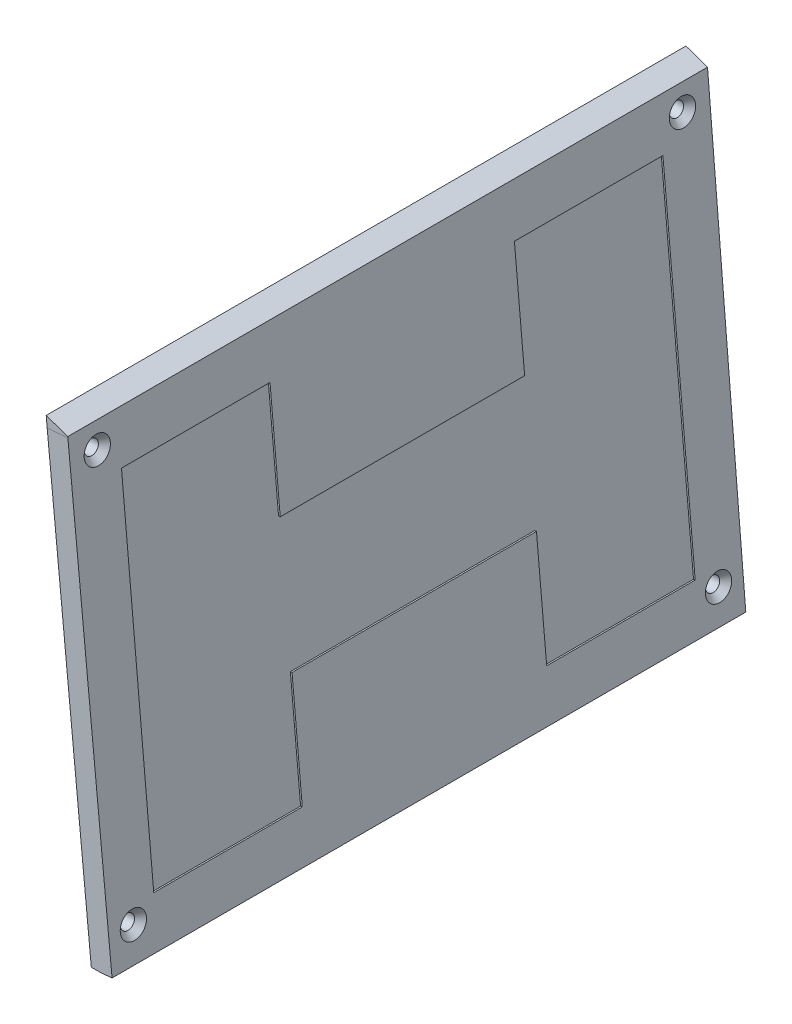
SolidWorks part; units mm, degrees
ref_plane "Front Plane" through (0, 0, 0) normal (0, 0, 1) x (1, 0, 0)
ref_plane "Top Plane" through (0, 0, 0) normal (0, 1, 0) x (1, 0, 0)
ref_plane "Right Plane" through (0, 0, 0) normal (1, 0, 0) x (0, 0, -1)
sketch "Sketch3" plane through (0, 0, 0) normal (0, 1, 0) x (1, 0, 0)
  line L1 (-180, 95) -> (180, 95)
  line L2 (-180, 95) -> (-180, -95)
  line L3 (-180, -95) -> (180, -95)
  line L4 (180, 95) -> (180, -95)
  line L5 (-180, 95) -> (180, -95) construction
  line L6 (-180, -95) -> (180, 95) construction
  point P0 (0, 0)
  dimension "D1" = 190
  dimension "D2" = 360
extrude "Boss-Extrude2" add sketch "Sketch3" along normal blind 158
sketch "Sketch4" plane through (180, 0, 0) normal (1, 0, 0) x (0, 0, -1)
  line L0 (-95, 0) -> (-95, 158)
  line L1 (-95, 158) -> (-85, 158)
  line L2 (-95, 158) -> (95, 158) construction
  line L3 (-85, 158) -> (-95, 0)
  line L4 (0, 0) -> (0, 123.75) construction
  line L5 (85, 158) -> (95, 0)
  line L6 (95, 158) -> (85, 158)
  line L7 (95, 0) -> (95, 158)
  dimension "D1" = 170
extrude "Cut-Extrude1" cut sketch "Sketch4" against normal through all
sketch "Sketch5" plane through (0, 0, 0) normal (0, 0, 1) x (1, 0, 0)
  line L0 (-180, 0) -> (-165.5, 158)
  line L1 (-180, 158) -> (180, 158) construction
  line L2 (-165.5, 158) -> (-180, 158)
  line L3 (-180, 158) -> (-180, 0)
  line L4 (0, 0) -> (0, 158) construction
  line L5 (180, 158) -> (180, 0)
  line L6 (165.5, 158) -> (180, 158)
  line L7 (180, 0) -> (165.5, 158)
  dimension "D1" = 331
extrude "Cut-Extrude2" cut sketch "Sketch5" against normal through all both and the other way through all
sketch "Sketch6" plane through (0, 0, 0) normal (0, 0, 1) x (1, 0, 0)
  line L0 (180, 0) -> (180, 105) construction
  line L2 (-165.5, 158) -> (165.5, 158) construction
  line L3 (64, 145.6686) -> (180, 105)
  line L4 (180, 105) -> (180, 158)
  line L5 (-180, 110) -> (-180, 158)
  line L6 (-180, 158) -> (-97, 158)
  line L8 (-180, 0) -> (-180, 110) construction
  line L9 (64, 145.6686) -> (64, 158)
  line L10 (64, 158) -> (180, 158)
  line L11 (-180, 110) -> (-97, 145.6686)
  line L12 (-97, 145.6686) -> (-97, 158)
  dimension "D1" = 105
  dimension "D2" = 110
  dimension "D3" = 83
  dimension "D4" = 116
extrude "Cut-Extrude3" cut sketch "Sketch6" along normal through all both and the other way through all
sketch "Sketch8" plane through (0, 0, 0) normal (0, 1, 0) x (1, 0, 0)
  line L0 (-180, 76.5) -> (-97, 85)
  line L3 (-180, 95) -> (-180, -95) construction
  line L4 (-180, 111.8161) -> (-180, 76.5)
  line L5 (0, 0) -> (-198.7212, 0) construction
  line L11 (-180, 111.8161) -> (-97, 111.8161)
  line L12 (-97, 111.8161) -> (-97, 85)
  line L13 (-97, -111.8161) -> (-97, -85)
  line L14 (-180, -111.8161) -> (-97, -111.8161)
  line L15 (-180, -111.8161) -> (-180, -76.5)
  line L16 (-180, -76.5) -> (-97, -85)
  line L17 (64, 85) -> (64, 140.1812)
  line L18 (64, 85) -> (180, 76.5)
  line L19 (180, 76.5) -> (197.104, 166.0233)
  line L20 (197.104, 166.0233) -> (64, 140.1812)
  line L21 (197.104, -166.0233) -> (64, -140.1812)
  line L22 (180, -76.5) -> (197.104, -166.0233)
  line L23 (64, -85) -> (180, -76.5)
  line L24 (64, -85) -> (64, -140.1812)
  line L29 (180, -95) -> (180, 95) construction
  dimension "D1" = 153
extrude "Cut-Extrude4" cut sketch "Sketch8" against normal through all and the other way through all
sketch "Sketch10" plane through (0, 0, 0) normal (0, -1, 0) x (1, 0, 0)
  line L1 (-156.5, -79) -> (156.5, -79) construction
  line L2 (-156.5, -79) -> (-156.5, 79) construction
  line L3 (-156.5, 79) -> (156.5, 79) construction
  line L4 (156.5, -79) -> (156.5, 79) construction
  line L5 (-156.5, -79) -> (156.5, 79) construction
  line L6 (-156.5, 79) -> (156.5, -79) construction
  point P0 (0, 0)
  dimension "D1" = 313
  dimension "D2" = 158
shell "Shell6" thickness 5 removed face at (-11, 0, 0)
sketch "Sketch11" plane through (0, 0, 0) normal (0, -1, 0) x (1, 0, 0)
  line L0 (-97, 95) -> (64, 95) construction
  line L1 (-97, 95) -> (64, 95)
  line L14 (-97, 95) -> (-97, 85)
  line L15 (-97, 85) -> (-180, 76.5)
  line L16 (-180, 76.5) -> (-180, -76.5)
  line L17 (-180, -76.5) -> (-97, -85)
  line L18 (-97, -85) -> (-97, -95)
  line L19 (-97, -95) -> (64, -95)
  line L20 (64, -95) -> (64, -85)
  line L21 (64, -85) -> (180, -76.5)
  line L22 (180, -76.5) -> (180, 76.5)
  line L23 (180, 76.5) -> (64, 85)
  line L24 (64, 85) -> (64, 95)
  line L25 (64, 95) -> (-97, 95)
  line L26 (-97, 95) -> (-97, 85)
  line L27 (-97, 85) -> (-180, 76.5)
  line L28 (-180, 76.5) -> (-180, -76.5)
  line L29 (-180, -76.5) -> (-97, -85)
  line L30 (-97, -85) -> (-97, -95)
  line L31 (-97, -95) -> (64, -95)
  line L32 (64, -95) -> (64, -85)
  line L33 (64, -85) -> (180, -76.5)
  line L34 (180, -76.5) -> (180, 76.5)
  line L35 (180, 76.5) -> (64, 85)
  line L36 (64, 85) -> (64, 95)
  line L37 (64, 95) -> (-97, 95)
  line M25 (-92, 80.4859) -> (-92, 89.99)
  line M26 (-92, 89.99) -> (59, 89.99)
  line M27 (59, 89.99) -> (59, 80.353)
  line M28 (59, 80.353) -> (174.979, 71.8545)
  line M29 (174.979, 71.8545) -> (174.979, -71.8545)
  line M30 (174.979, -71.8545) -> (59, -80.353)
  line M31 (59, -80.353) -> (59, -89.99)
  line M32 (59, -89.99) -> (-92, -89.99)
  line M33 (-92, -89.99) -> (-92, -80.4859)
  line M34 (-92, -80.4859) -> (-174.979, -71.988)
  line M35 (-174.979, -71.988) -> (-174.979, 71.988)
  line M36 (-174.979, 71.988) -> (-92, 80.4859)
  dimension "D1" = 0
extrude "Boss-Extrude3" add sketch "Sketch11" against normal blind 5 contours M25 M36 M35 M34 M33 M32 M31 M30 M29 M28 M27 M26 region at (-1.4169, 0, 0)
chamfer "Chamfer1" distance 19.9 angle 25 2 edges at (-97, 72.8343, -85) (64, 72.8343, 85) first distance on face at (-97, 75.9172, 0) first distance on face at (64, 75.9172, 0)
chamfer "Chamfer2" distance 19.9 angle 25 2 edges at (-97, 72.8343, 85) (64, 72.8343, -85) first distance on face at (-97, 101.2229, 29.8699) first distance on face at (64, 101.2229, -29.8699)
chamfer "Chamfer3" distance 10 angle 45 2 edges at (73.6078, 71.1501, -84.296) (-106.7449, 70.7404, 84.002) first distance on face at (124.3148, 62.6977, -80.5804) first distance on face at (-140.7451, 63.9993, 80.5201)
chamfer "Chamfer4" distance 5 angle 50 1 edges at (-97, 145.6686, 0) first distance on face at (-122.0326, 134.911, -0.0994)
chamfer "Chamfer5" distance 6 angle 50 1 edges at (64, 145.6686, 0) first distance on face at (97.4296, 133.9485, 0.0677)
sketch "Sketch18" plane through (-9.6212, 0, 93.9484) normal (-0.1019, 0, 0.9948) x (0.9948, 0, 0.1019)
  line L0 (-160.4966, 116.7807) -> (-170.6066, 7.1902)
  line L1 (-171.2699, 0) -> (-160.7055, 114.5163) construction
  line L2 (-170.6066, 7.1902) -> (-129.9277, 7.1902)
  line L3 (-129.9277, 7.1902) -> (-126.2803, 17.3621)
  line L4 (-126.2803, 17.3621) -> (-115.3442, 17.3621)
  line L5 (-115.3442, 17.3621) -> (-115.3442, 136.0837)
  line L7 (-115.3442, 136.0837) -> (-160.4966, 116.7807)
  line L11 (-107.6316, 0) -> (-171.2699, 0) construction
  line L12 (-107.6316, 0) -> (-107.6316, 137.2058) construction
  line L14 (-107.6316, 137.2058) -> (-160.7055, 114.5163) construction
  dimension "D1" = 2
extrude "Boss-Extrude5" add sketch "Sketch18" along normal blind 2
sketch "Sketch19" plane through (-9.825, 0, 95.938) normal (-0.1019, 0, 0.9948) x (0.9948, 0, 0.1019)
  line L0 (-144.8175, 92.3146) -> (-144.8175, 71.3428)
  line L1 (-143.3175, 94.3146) -> (-122.3457, 94.3146)
  line L2 (-145.3175, 92.3146) -> (-145.3175, 71.3428)
  line L3 (-143.3175, 69.3428) -> (-122.3457, 69.3428)
  line L4 (-120.3457, 92.3146) -> (-120.3457, 71.3428)
  line L5 (-145.3175, 94.3146) -> (-122.3457, 69.3428) construction
  line L6 (-145.3175, 69.3428) -> (-120.3457, 94.3146) construction
  line L7 (-143.3175, 69.8428) -> (-122.3457, 69.8428)
  line L8 (-120.8457, 92.3146) -> (-120.8457, 71.3428)
  line L9 (-143.3175, 93.8146) -> (-122.3457, 93.8146)
  arc A0 (-122.3457, 94.3146) -> (-120.3457, 92.3146) centre (-122.3457, 92.3146) cw
  arc A1 (-122.3457, 69.3428) -> (-120.3457, 71.3428) centre (-122.3457, 71.3428) ccw
  arc A2 (-145.3175, 71.3428) -> (-143.3175, 69.3428) centre (-143.3175, 71.3428) ccw
  arc A3 (-143.3175, 94.3146) -> (-145.3175, 92.3146) centre (-143.3175, 92.3146) ccw
  arc A4 (-144.8175, 71.3428) -> (-143.3175, 69.8428) centre (-143.3175, 71.3428) ccw
  arc A5 (-122.3457, 69.8428) -> (-120.8457, 71.3428) centre (-122.3457, 71.3428) ccw
  arc A6 (-122.3457, 93.8146) -> (-120.8457, 92.3146) centre (-122.3457, 92.3146) cw
  arc A7 (-143.3175, 93.8146) -> (-144.8175, 92.3146) centre (-143.3175, 92.3146) ccw
  point P0 (-133.3524, 81.3079)
  dimension "D1" = 2
  dimension "D2" = 0.5
extrude "Cut-Extrude5" cut sketch "Sketch19" against normal blind 0.5
sketch "Sketch20" plane through (0, 5.9887, 94.621) normal (0, 0.0632, 0.998) x (1, 0, 0)
  line L0 (-89.2026, 82.2629) -> (-89.2026, 21.0896)
  line L1 (-86.7026, 83.7629) -> (58.7101, 83.7629)
  line L2 (-88.7026, 81.7629) -> (-88.7026, 21.5896)
  line L3 (-86.7026, 19.5896) -> (58.7101, 19.5896)
  line L4 (60.7101, 81.7629) -> (60.7101, 21.5896)
  line L5 (-88.7026, 83.7629) -> (60.7101, 19.5896) construction
  line L6 (-88.7026, 19.5896) -> (60.7101, 83.7629) construction
  line L7 (-87.2026, 19.0896) -> (59.2101, 19.0896)
  line L8 (61.2101, 82.2629) -> (61.2101, 21.0896)
  line L9 (-87.2026, 84.2629) -> (59.2101, 84.2629)
  line L10 (61.2101, 84.2629) -> (61.2101, 19.0896) construction
  line L11 (-89.2026, 84.2629) -> (61.2101, 84.2629) construction
  line L12 (-88.7026, 83.7629) -> (60.7101, 83.7629) construction
  line L13 (60.7101, 83.7629) -> (60.7101, 19.5896) construction
  line L14 (-88.7026, 19.5896) -> (60.7101, 19.5896) construction
  line L15 (-89.2026, 19.0896) -> (61.2101, 19.0896) construction
  line L16 (-89.2026, 84.2629) -> (-89.2026, 19.0896) construction
  line L17 (-88.7026, 83.7629) -> (-88.7026, 19.5896) construction
  arc A0 (61.2101, 82.2629) -> (59.2101, 84.2629) centre (59.2101, 82.2629) ccw
  arc A1 (58.7101, 83.7629) -> (60.7101, 81.7629) centre (58.7101, 81.7629) cw
  arc A2 (58.7101, 19.5896) -> (60.7101, 21.5896) centre (58.7101, 21.5896) ccw
  arc A3 (59.2101, 19.0896) -> (61.2101, 21.0896) centre (59.2101, 21.0896) ccw
  arc A4 (-89.2026, 21.0896) -> (-87.2026, 19.0896) centre (-87.2026, 21.0896) ccw
  arc A5 (-88.7026, 21.5896) -> (-86.7026, 19.5896) centre (-86.7026, 21.5896) ccw
  arc A6 (-89.2026, 82.2629) -> (-87.2026, 84.2629) centre (-87.2026, 82.2629) cw
  arc A7 (-86.7026, 83.7629) -> (-88.7026, 81.7629) centre (-86.7026, 81.7629) ccw
  point P0 (-13.9963, 51.6763)
  dimension "D2" = 2
  dimension "D1" = 0.5
extrude "Cut-Extrude6" cut sketch "Sketch20" against normal blind 0.5
sketch "Sketch21" plane through (6.537, 0, 89.2107) normal (0.0731, 0, 0.9973) x (0.9973, 0, -0.0731)
  line L0 (78.6105, 140.2638) -> (78.6105, 9.5077)
  line L2 (163.945, 108.4906) -> (173.9281, 0) construction
  line L3 (171.9049, 21.987) -> (163.7609, 110.4906)
  line L4 (163.7609, 110.4906) -> (78.6105, 140.2638)
  line L6 (67.2506, 142.3002) -> (67.2506, 0) construction
  line L8 (78.6105, 9.5077) -> (125.3303, 9.5077)
  line L9 (125.3303, 9.5077) -> (138.5436, 21.987)
  line L10 (138.5436, 21.987) -> (171.9049, 21.987)
  line L11 (163.945, 108.4906) -> (67.2506, 142.3002) construction
  line L12 (163.945, 108.4906) -> (175.2328, 108.4906) construction
  dimension "D1" = 2
extrude "Boss-Extrude6" add sketch "Sketch21" along normal blind 2
sketch "Sketch22" plane through (6.6831, 0, 91.2053) normal (0.0731, 0, 0.9973) x (0.9973, 0, -0.0731)
  line L0 (99.9186, 58.3939) -> (99.9186, 31.5005)
  line L1 (90.1817, 112.8938) -> (113.9275, 112.8938)
  line L2 (88.1817, 110.8938) -> (88.1817, 86.2383)
  line L3 (90.1817, 84.2383) -> (113.9275, 84.2383)
  line L4 (115.9275, 110.8938) -> (115.9275, 86.2383)
  line L5 (88.1817, 112.8938) -> (115.9275, 84.2383) construction
  line L6 (88.1817, 84.2383) -> (115.9275, 112.8938) construction
  line L7 (102.4186, 60.3939) -> (157.9396, 60.3939)
  line L8 (100.4186, 58.3939) -> (100.4186, 31.5005)
  line L9 (102.4186, 29.5005) -> (157.9396, 29.5005)
  line L10 (159.9396, 58.3939) -> (159.9396, 31.5005)
  line L11 (100.4186, 60.3939) -> (159.9396, 29.5005) construction
  line L12 (100.4186, 29.5005) -> (159.9396, 60.3939) construction
  line L13 (144.9909, 57.8533) -> (153.382, 57.8533)
  line L14 (143.9909, 56.8533) -> (143.9909, 52.772)
  line L15 (144.9909, 51.772) -> (153.382, 51.772)
  line L16 (154.382, 56.8533) -> (154.382, 52.772)
  line L17 (143.9909, 57.8533) -> (154.382, 51.772) construction
  line L18 (143.9909, 51.772) -> (154.382, 57.8533) construction
  line L19 (144.9909, 38.1224) -> (153.382, 38.1224)
  line L20 (143.9909, 37.1224) -> (143.9909, 33.0411)
  line L21 (144.9909, 32.0411) -> (153.382, 32.0411)
  line L22 (154.382, 37.1224) -> (154.382, 33.0411)
  line L23 (143.9909, 38.1224) -> (154.382, 32.0411) construction
  line L24 (143.9909, 32.0411) -> (154.382, 38.1224) construction
  line L25 (102.4186, 29.0005) -> (157.9396, 29.0005)
  line L26 (160.4396, 58.3939) -> (160.4396, 31.5005)
  line L27 (102.4186, 60.8939) -> (157.9396, 60.8939)
  line L28 (87.6817, 110.8938) -> (87.6817, 86.2383)
  line L29 (90.1817, 83.7383) -> (113.9275, 83.7383)
  line L30 (116.4275, 110.8938) -> (116.4275, 86.2383)
  line L31 (90.1817, 113.3938) -> (113.9275, 113.3938)
  line L32 (143.4909, 56.8533) -> (143.4909, 52.772)
  line L33 (144.9909, 51.272) -> (153.382, 51.272)
  line L34 (154.882, 56.8533) -> (154.882, 52.772)
  line L35 (144.9909, 58.3533) -> (153.382, 58.3533)
  line L36 (143.4909, 37.1224) -> (143.4909, 33.0411)
  line L37 (144.9909, 31.5411) -> (153.382, 31.5411)
  line L38 (154.882, 37.1224) -> (154.882, 33.0411)
  line L39 (144.9909, 38.6224) -> (153.382, 38.6224)
  arc A0 (157.9396, 60.3939) -> (159.9396, 58.3939) centre (157.9396, 58.3939) cw
  arc A1 (157.9396, 29.5005) -> (159.9396, 31.5005) centre (157.9396, 31.5005) ccw
  arc A2 (100.4186, 31.5005) -> (102.4186, 29.5005) centre (102.4186, 31.5005) ccw
  arc A3 (102.4186, 60.3939) -> (100.4186, 58.3939) centre (102.4186, 58.3939) ccw
  arc A4 (113.9275, 112.8938) -> (115.9275, 110.8938) centre (113.9275, 110.8938) cw
  arc A5 (113.9275, 84.2383) -> (115.9275, 86.2383) centre (113.9275, 86.2383) ccw
  arc A6 (88.1817, 86.2383) -> (90.1817, 84.2383) centre (90.1817, 86.2383) ccw
  arc A7 (90.1817, 112.8938) -> (88.1817, 110.8938) centre (90.1817, 110.8938) ccw
  arc A8 (143.9909, 33.0411) -> (144.9909, 32.0411) centre (144.9909, 33.0411) ccw
  arc A9 (153.382, 38.1224) -> (154.382, 37.1224) centre (153.382, 37.1224) cw
  arc A10 (153.382, 32.0411) -> (154.382, 33.0411) centre (153.382, 33.0411) ccw
  arc A11 (144.9909, 38.1224) -> (143.9909, 37.1224) centre (144.9909, 37.1224) ccw
  arc A12 (143.9909, 52.772) -> (144.9909, 51.772) centre (144.9909, 52.772) ccw
  arc A13 (153.382, 51.772) -> (154.382, 52.772) centre (153.382, 52.772) ccw
  arc A14 (153.382, 57.8533) -> (154.382, 56.8533) centre (153.382, 56.8533) cw
  arc A15 (144.9909, 57.8533) -> (143.9909, 56.8533) centre (144.9909, 56.8533) ccw
  arc A16 (99.9186, 31.5005) -> (102.4186, 29.0005) centre (102.4186, 31.5005) ccw
  arc A17 (157.9396, 29.0005) -> (160.4396, 31.5005) centre (157.9396, 31.5005) ccw
  arc A18 (157.9396, 60.8939) -> (160.4396, 58.3939) centre (157.9396, 58.3939) cw
  arc A19 (102.4186, 60.8939) -> (99.9186, 58.3939) centre (102.4186, 58.3939) ccw
  arc A20 (87.6817, 86.2383) -> (90.1817, 83.7383) centre (90.1817, 86.2383) ccw
  arc A21 (113.9275, 83.7383) -> (116.4275, 86.2383) centre (113.9275, 86.2383) ccw
  arc A22 (113.9275, 113.3938) -> (116.4275, 110.8938) centre (113.9275, 110.8938) cw
  arc A23 (90.1817, 113.3938) -> (87.6817, 110.8938) centre (90.1817, 110.8938) ccw
  arc A24 (143.4909, 52.772) -> (144.9909, 51.272) centre (144.9909, 52.772) ccw
  arc A25 (153.382, 51.272) -> (154.882, 52.772) centre (153.382, 52.772) ccw
  arc A26 (153.382, 58.3533) -> (154.882, 56.8533) centre (153.382, 56.8533) cw
  arc A27 (144.9909, 58.3533) -> (143.4909, 56.8533) centre (144.9909, 56.8533) ccw
  arc A28 (143.4909, 33.0411) -> (144.9909, 31.5411) centre (144.9909, 33.0411) ccw
  arc A29 (153.382, 31.5411) -> (154.882, 33.0411) centre (153.382, 33.0411) ccw
  arc A30 (153.382, 38.6224) -> (154.882, 37.1224) centre (153.382, 37.1224) cw
  arc A31 (144.9909, 38.6224) -> (143.4909, 37.1224) centre (144.9909, 37.1224) ccw
  point P0 (102.0546, 98.566)
  point P5 (130.1791, 44.9472)
  point P10 (149.1865, 35.0818)
  point P11 (149.1865, 54.8126)
  dimension "D1" = 2
  dimension "D2" = 1
  dimension "D3" = 0.5
  dimension "D4" = 0.5
  dimension "D5" = 0.5
  dimension "D6" = 0.5
extrude "Cut-Extrude7" cut sketch "Sketch22" against normal blind 0.5 contours L31 A23 L28 A20 L29 A21 L30 A22 A7 L1 A4 L4 A5 L3 A6 L2 | L27 A19 L0 A16 L25 A17 L26 A18 A3 L7 A0 L10 A1 L9 A2 L8 | L35 A27 L32 A24 L33 A25 L34 A26 A15 L13 A14 L16 A13 L15 A12 L14 | L39 A31 L36 A28 L37 A29 L38 A30 A11 L19 A9 L22 A10 L21 A8 L20 region at (107.1131, 60.1133, 83.8462) region at (95.152, 112.3695, 84.7227) region at (150.3231, 57.8191, 80.68) region at (150.3231, 38.0882, 80.68)
sketch "Sketch23" plane through (0, 5.9887, 94.621) normal (0, 0.0632, 0.998) x (1, 0, 0)
  line L0 (35.4779, 68.5836) -> (50.4779, 68.5836) construction
  line L1 (35.4779, 69.3336) -> (50.4779, 69.3336)
  line L2 (35.4779, 67.8336) -> (50.4779, 67.8336)
  line L3 (42.9779, 68.5836) -> (42.9779, 41.1335) construction
  line L4 (35.4779, 64.5836) -> (50.4779, 64.5836) construction
  line L5 (35.4779, 65.3336) -> (50.4779, 65.3336)
  line L6 (35.4779, 63.8336) -> (50.4779, 63.8336)
  line L7 (35.4779, 60.5836) -> (50.4779, 60.5836) construction
  line L8 (35.4779, 61.3336) -> (50.4779, 61.3336)
  line L9 (35.4779, 59.8336) -> (50.4779, 59.8336)
  line L10 (35.4779, 56.5836) -> (50.4779, 56.5836) construction
  line L11 (35.4779, 57.3336) -> (50.4779, 57.3336)
  line L12 (35.4779, 55.8336) -> (50.4779, 55.8336)
  line L13 (35.4779, 52.5836) -> (50.4779, 52.5836) construction
  line L14 (35.4779, 53.3336) -> (50.4779, 53.3336)
  line L15 (35.4779, 51.8336) -> (50.4779, 51.8336)
  line L16 (35.4779, 48.5836) -> (50.4779, 48.5836) construction
  line L17 (35.4779, 49.3336) -> (50.4779, 49.3336)
  line L18 (35.4779, 47.8336) -> (50.4779, 47.8336)
  line L19 (35.4779, 44.5836) -> (50.4779, 44.5836) construction
  line L20 (35.4779, 45.3336) -> (50.4779, 45.3336)
  line L21 (35.4779, 43.8336) -> (50.4779, 43.8336)
  line L22 (35.4779, 40.5836) -> (50.4779, 40.5836) construction
  line L23 (35.4779, 41.3336) -> (50.4779, 41.3336)
  line L24 (35.4779, 39.8336) -> (50.4779, 39.8336)
  line L25 (35.4779, 36.5836) -> (50.4779, 36.5836) construction
  line L26 (35.4779, 37.3336) -> (50.4779, 37.3336)
  line L27 (35.4779, 35.8336) -> (50.4779, 35.8336)
  line L28 (35.4779, 32.5836) -> (50.4779, 32.5836) construction
  line L29 (35.4779, 33.3336) -> (50.4779, 33.3336)
  line L30 (35.4779, 31.8336) -> (50.4779, 31.8336)
  arc A0 (35.4779, 69.3336) -> (35.4779, 67.8336) centre (35.4779, 68.5836) ccw
  arc A1 (50.4779, 67.8336) -> (50.4779, 69.3336) centre (50.4779, 68.5836) ccw
  arc A2 (35.4779, 65.3336) -> (35.4779, 63.8336) centre (35.4779, 64.5836) ccw
  arc A3 (50.4779, 63.8336) -> (50.4779, 65.3336) centre (50.4779, 64.5836) ccw
  arc A4 (35.4779, 61.3336) -> (35.4779, 59.8336) centre (35.4779, 60.5836) ccw
  arc A5 (50.4779, 59.8336) -> (50.4779, 61.3336) centre (50.4779, 60.5836) ccw
  arc A6 (35.4779, 57.3336) -> (35.4779, 55.8336) centre (35.4779, 56.5836) ccw
  arc A7 (50.4779, 55.8336) -> (50.4779, 57.3336) centre (50.4779, 56.5836) ccw
  arc A8 (35.4779, 53.3336) -> (35.4779, 51.8336) centre (35.4779, 52.5836) ccw
  arc A9 (50.4779, 51.8336) -> (50.4779, 53.3336) centre (50.4779, 52.5836) ccw
  arc A10 (35.4779, 49.3336) -> (35.4779, 47.8336) centre (35.4779, 48.5836) ccw
  arc A11 (50.4779, 47.8336) -> (50.4779, 49.3336) centre (50.4779, 48.5836) ccw
  arc A12 (35.4779, 45.3336) -> (35.4779, 43.8336) centre (35.4779, 44.5836) ccw
  arc A13 (50.4779, 43.8336) -> (50.4779, 45.3336) centre (50.4779, 44.5836) ccw
  arc A14 (35.4779, 41.3336) -> (35.4779, 39.8336) centre (35.4779, 40.5836) ccw
  arc A15 (50.4779, 39.8336) -> (50.4779, 41.3336) centre (50.4779, 40.5836) ccw
  arc A16 (35.4779, 37.3336) -> (35.4779, 35.8336) centre (35.4779, 36.5836) ccw
  arc A17 (50.4779, 35.8336) -> (50.4779, 37.3336) centre (50.4779, 36.5836) ccw
  arc A18 (35.4779, 33.3336) -> (35.4779, 31.8336) centre (35.4779, 32.5836) ccw
  arc A19 (50.4779, 31.8336) -> (50.4779, 33.3336) centre (50.4779, 32.5836) ccw
  point P2 (42.9779, 68.5836)
  point P13 (42.9779, 64.5836)
  point P20 (42.9779, 60.5836)
  point P27 (42.9779, 56.5836)
  point P34 (42.9779, 52.5836)
  point P41 (42.9779, 48.5836)
  point P48 (42.9779, 44.5836)
  point P55 (42.9779, 40.5836)
  point P62 (42.9779, 36.5836)
  point P69 (42.9779, 32.5836)
  dimension "D1" = 1.5
  dimension "D2" = 15
  dimension "D4" = 4
  dimension "D3" = 10
extrude "Cut-Extrude8" cut sketch "Sketch23" against normal up to next
sketch "Sketch24" plane through (-132.805, 39.9565, 0) normal (-0.9576, 0.2881, 0) x (0, 0, 1)
  line L0 (0, 0) -> (0, 138.6299) construction
  line L1 (-70.0038, 121.648) -> (-70.0038, 110.9297)
  line L2 (-74.0038, 121.648) -> (-22.0038, 121.648)
  line L3 (-74.0038, 121.648) -> (-74.0038, 110.9297)
  line L4 (-74.0038, 110.9297) -> (-22.0038, 110.9297)
  line L5 (-22.0038, 121.648) -> (-22.0038, 110.9297)
  line L6 (-74.0038, 121.648) -> (-22.0038, 110.9297) construction
  line L7 (-74.0038, 110.9297) -> (-22.0038, 121.648) construction
  line L8 (-66.0038, 121.648) -> (-66.0038, 110.9297)
  line L9 (-62.0038, 121.648) -> (-62.0038, 110.9297)
  line L10 (-58.0038, 121.648) -> (-58.0038, 110.9297)
  line L11 (-54.0038, 121.648) -> (-54.0038, 110.9297)
  line L12 (-50.0038, 121.648) -> (-50.0038, 110.9297)
  line L13 (-46.0038, 121.648) -> (-46.0038, 110.9297)
  line L14 (-42.0038, 121.648) -> (-42.0038, 110.9297)
  line L15 (-38.0038, 121.648) -> (-38.0038, 110.9297)
  line L16 (-34.0038, 121.648) -> (-34.0038, 110.9297)
  line L17 (-30.0038, 121.648) -> (-30.0038, 110.9297)
  line L18 (-26.0038, 121.648) -> (-26.0038, 110.9297)
  line L19 (-22.0038, 121.648) -> (-22.0038, 110.9297)
  point P3 (-48.0038, 116.2888)
  dimension "D2" = 52
  dimension "D3" = 4
  dimension "D4" = 4
  dimension "D1" = 13
extrude "Cut-Extrude9" cut sketch "Sketch24" against normal up to next contours L3 L4 L1 L2 | L9 L2 L8 L4 | L11 L2 L10 L4 | L13 L2 L12 L4 | L15 L2 L14 L4 | L17 L2 L16 L4 | L2 L18 L4 L5
mirror "Mirror1" about plane through (0, 0, 0) normal (0, 0, 1) of "Cut-Extrude9", "Cut-Extrude7", "Cut-Extrude6", "Cut-Extrude5", "Boss-Extrude5", "Boss-Extrude6", "Cut-Extrude8"
sketch "Sketch25" plane through (-178.4967, 16.381, 0) normal (-0.9958, 0.0914, 0) x (0, 0, 1)
  line L12 (-73.5279, -13.4499) -> (73.5279, -13.4499)
  line L13 (73.5677, -9.2014) -> (74.5481, 95.5477)
  line L14 (74.5481, 95.5477) -> (-74.5481, 95.5477)
  line L15 (-74.5481, 95.5477) -> (-73.5677, -9.2014)
  line L16 (-73.5279, -13.4499) -> (73.5279, -13.4499)
  line L17 (73.5677, -9.2014) -> (74.5481, 95.5477)
  line L18 (74.5481, 95.5477) -> (-74.5481, 95.5477)
  line L19 (-74.5481, 95.5477) -> (-73.5677, -9.2014)
  line L20 (73.5279, -13.4499) -> (73.5677, -9.2014)
  line L21 (73.5279, -13.4499) -> (73.5677, -9.2014)
  line L22 (-73.5677, -9.2014) -> (-73.5279, -13.4499)
  line L23 (-73.5677, -9.2014) -> (-73.5279, -13.4499)
  dimension "D1" = 3
extrude "Cut-Extrude10" cut sketch "Sketch25" against normal blind 1
sketch "Sketch26" plane through (52.4855, 149.7055, 0) normal (0.3308, 0.9437, 0) x (0.9437, -0.3308, 0)
  line L0 (93.9118, -72.9864) -> (93.9118, -24.3785)
  line L5 (93.9118, -24.3785) -> (42.7728, -19.9044)
  line L6 (42.7728, -19.9044) -> (42.7728, -77.4604)
  line L8 (42.7728, -77.4604) -> (93.9118, -72.9864)
  ellipse E0 centre (67.5901, -66.9324) end of major axis (62.2316, -67.5868) minor radius 2.6176
  dimension "D1" = 95
extrude "Cut-Extrude11" cut sketch "Sketch26" against normal blind 0.5 contours L6 L8 L0 L5 E0 region at (116.3016, 127.3321, 48.379)
sketch "Sketch29" plane through (178.4967, 16.381, 0) normal (0.9958, 0.0914, 0) x (0, 0, -1)
  line L0 (-65.1489, 80.4967) -> (-65.1489, -4.4499)
  line L1 (-65.1489, -4.4499) -> (-29.4086, -4.4499)
  line L2 (-29.4086, -4.4499) -> (-29.4086, 22.4535)
  line L3 (-29.4086, 22.4535) -> (29.4086, 22.4535)
  line L4 (29.4086, 22.4535) -> (29.4086, -4.4499)
  line L5 (29.4086, -4.4499) -> (65.1489, -4.4499)
  line L6 (65.1489, -4.4499) -> (65.1489, 80.4967)
  line L7 (65.1489, 80.4967) -> (29.4086, 80.4967)
  line L8 (29.4086, 80.4967) -> (29.4086, 53.5933)
  line L9 (29.4086, 53.5933) -> (-29.4086, 53.5933)
  line L10 (-29.4086, 53.5933) -> (-29.4086, 80.4967)
  line L11 (-29.4086, 80.4967) -> (-65.1489, 80.4967)
  line L12 (-77.2296, 92.4967) -> (-76.6479, 5.6295) construction
  line L13 (76.6479, 5.6295) -> (77.2296, 92.4967) construction
  line L14 (0, 0) -> (0, 84.8161) construction
  line L15 (-77.2296, 92.4967) -> (77.2296, 92.4967) construction
  line L16 (-76.5, -16.4499) -> (76.5, -16.4499) construction
  point P23 (0, 0)
  point P24 (29.6712, 23.9221)
  point P25 (-29.4086, 53.5933)
  dimension "D1" = 12
  dimension "D2" = 12
  dimension "D3" = 12
  dimension "D4" = 12
extrude "Cut-Extrude12" cut sketch "Sketch29" against normal blind 0.4
sketch "Sketch31" plane through (0, 0, 0) normal (0, 0, 1) x (1, 0, 0)
  line L1 (0, 0) -> (215.7861, 0)
  line L2 (0, 0) -> (0, 167.887)
  line L3 (0, 167.887) -> (215.7861, 167.887)
  line L4 (215.7861, 0) -> (215.7861, 167.887)
sketch "Sketch32" plane through (0, 0, 0) normal (0, 0, 1) x (1, 0, 0)
  line L1 (0, 0) -> (-188.9502, 0)
  line L2 (0, 0) -> (0, 184.6213)
  line L3 (0, 184.6213) -> (-188.9502, 184.6213)
  line L4 (-188.9502, 0) -> (-188.9502, 184.6213)
sketch "Sketch33" plane through (178.4967, 16.381, 0) normal (0.9958, 0.0914, 0) x (0, 0, -1)
  line L0 (-76.9779, 92.2467) -> (-76.9779, 101.3094)
  line L1 (-76.9779, 101.3094) -> (76.9779, 101.3094)
  line L2 (76.9779, 101.3094) -> (76.9779, 92.2467)
  line L7 (-170.0843, 187.4754) -> (186.8488, 187.4754)
  line L8 (-170.0843, 187.4754) -> (-170.0843, -37.1699)
  line L9 (-170.0843, -37.1699) -> (186.8488, -37.1699)
  line L10 (186.8488, 187.4754) -> (186.8488, -37.1699)
  line L12 (-76.2517, -16.1999) -> (76.2517, -16.1999)
  line L13 (76.2517, -16.1999) -> (76.3979, 5.6312)
  line L14 (76.3979, 5.6312) -> (76.9779, 92.2467)
  line L15 (76.9779, 92.2467) -> (-76.9779, 92.2467)
  line L16 (-76.9779, 92.2467) -> (-76.3979, 5.6312)
  line L17 (-76.3979, 5.6312) -> (-76.2517, -16.1999)
  line L18 (-76.2517, -16.1999) -> (76.2517, -16.1999)
  line L19 (76.2517, -16.1999) -> (76.3979, 5.6312)
  line L20 (76.3979, 5.6312) -> (76.9779, 92.2467)
  line L22 (-76.9779, 92.2467) -> (-76.3979, 5.6312)
  line L23 (-76.3979, 5.6312) -> (-76.2517, -16.1999)
  dimension "D1" = 0.25
extrude "Cut-Extrude13" cut sketch "Sketch33" against normal through all
sketch "Sketch34" plane through (1.4805, -16.1321, 0) normal (-0.0914, 0.9958, 0) x (0.9958, 0.0914, 0)
  line L7 (179.2468, -76.9779) -> (179.2468, 76.9779) construction
  line L8 (-230.0909, -173.9747) -> (174.2468, -173.9747)
  line L9 (-230.0909, -173.9747) -> (-230.0909, 160.6274)
  line L10 (-230.0909, 160.6274) -> (174.2468, 160.6274)
  line L11 (174.2468, -173.9747) -> (174.2468, 160.6274)
  dimension "D1" = 5
extrude "Cut-Extrude14" cut sketch "Sketch34" against normal through all both and the other way through all
sketch "Sketch35" plane through (173.5176, 15.9241, 0) normal (-0.9958, -0.0914, 0) x (0, 0, 1)
  line L0 (-76.2531, -15.991) -> (-76.9433, 124.4192)
  line L1 (-76.9433, 124.4192) -> (-105.1241, 114.9495)
  line L2 (-105.1241, 114.9495) -> (-98.7949, -15.991)
  line L3 (-98.7949, -15.991) -> (-76.2531, -15.991)
  line L4 (0, 0) -> (0, 138.6934) construction
  line L5 (98.7949, -15.991) -> (76.2531, -15.991)
  line L6 (105.1241, 114.9495) -> (98.7949, -15.991)
  line L7 (76.9433, 124.4192) -> (105.1241, 114.9495)
  line L8 (76.2531, -15.991) -> (76.9433, 124.4192)
  point P12 (-76.2531, -15.991)
extrude "Cut-Extrude15" cut sketch "Sketch35" against normal through all
sketch "Sketch36" plane through (178.4967, 16.381, 0) normal (0.9958, 0.0914, 0) x (0, 0, -1)
  line L0 (0, 0) -> (0, 129.5614) construction
  line L1 (-70.41, 86.6534) -> (70.41, 86.6534) construction
  line L2 (-70.41, 86.6534) -> (-70.41, -8.3466) construction
  line L3 (-70.41, -8.3466) -> (70.41, -8.3466) construction
  line L4 (70.41, 86.6534) -> (70.41, -8.3466) construction
  line L5 (-76.6148, 38.0234) -> (-55.8366, 38.0234) construction
  line L6 (-76.9779, 92.2467) -> (-76.2517, -16.1999) construction
  line L7 (-76.2517, -16.1999) -> (76.2517, -16.1999) construction
  circle A0 centre (-70.41, 86.6534) radius 3.9625
  circle A1 centre (70.41, 86.6534) radius 2.7177
  circle A2 centre (70.41, -8.3466) radius 2.4925
  circle A3 centre (-70.41, -8.3466) radius 3.9625
  dimension "D1" = 140.82
  dimension "D2" = 95
  dimension "D3" = 7.8533
hole_wizard "CSK for M3 Flat Head Machine Screw1" positions "3DSketch1" profile "Sketch37" countersink size "M3" standard "ANSI Metric" end condition through all
sketch3d "3DSketch1"
  point P0 (170.5776, 102.6718, 70.41)
  point P3 (179.2595, 8.0694, 70.41)
  point P6 (179.2595, 8.0694, -70.41)
  point P9 (170.5776, 102.6718, -70.41)
sketch "Sketch37" plane through (170.5776, 102.6718, 70.41) normal (0, 0, 1) x (-0.0914, 0.9958, 0)
  line L0 (0, 0) -> (0, 15.081)
  line L1 (0, 15.081) -> (1.7, 15.081)
  line L2 (1.7, 15.081) -> (1.7, 1.45)
  line L3 (1.7, 1.45) -> (3.15, 0)
  line L5 (3.15, 0) -> (0, 0)
  line L6 (-1.7, 1.45) -> (-3.15, 0) construction
  line L11 (0, -6.35) -> (0, 107.95) construction
  dimension "Thru Hole Dia." = 3.4
  dimension "Thru Hole Depth" = 15.081
  dimension "Near C'Sink Dia." = 6.3
  dimension "Near C'Sink Angle" = 90
